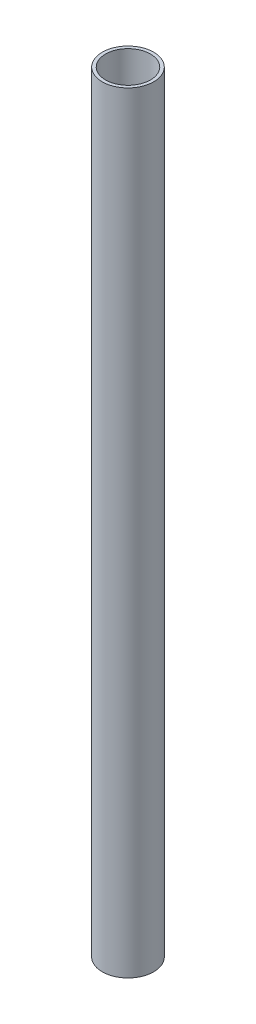
SolidWorks part; units mm, degrees
material "ASTM A36 Steel"
ref_plane "Front Plane" through (0, 0, 0) normal (0, 0, 1) x (1, 0, 0)
ref_plane "Top Plane" through (0, 0, 0) normal (0, 1, 0) x (1, 0, 0)
ref_plane "Right Plane" through (0, 0, 0) normal (1, 0, 0) x (0, 0, -1)
sketch "Sketch1" plane through (0, 0, 0) normal (0, 1, 0) x (1, 0, 0)
  circle A0 centre (0, 0) radius 44.45
  circle A1 centre (0, 0) radius 50.8
  dimension "D1" = 101.6
  dimension "D2" = 88.9
extrude "Boss-Extrude1" add sketch "Sketch1" along normal blind 1524
